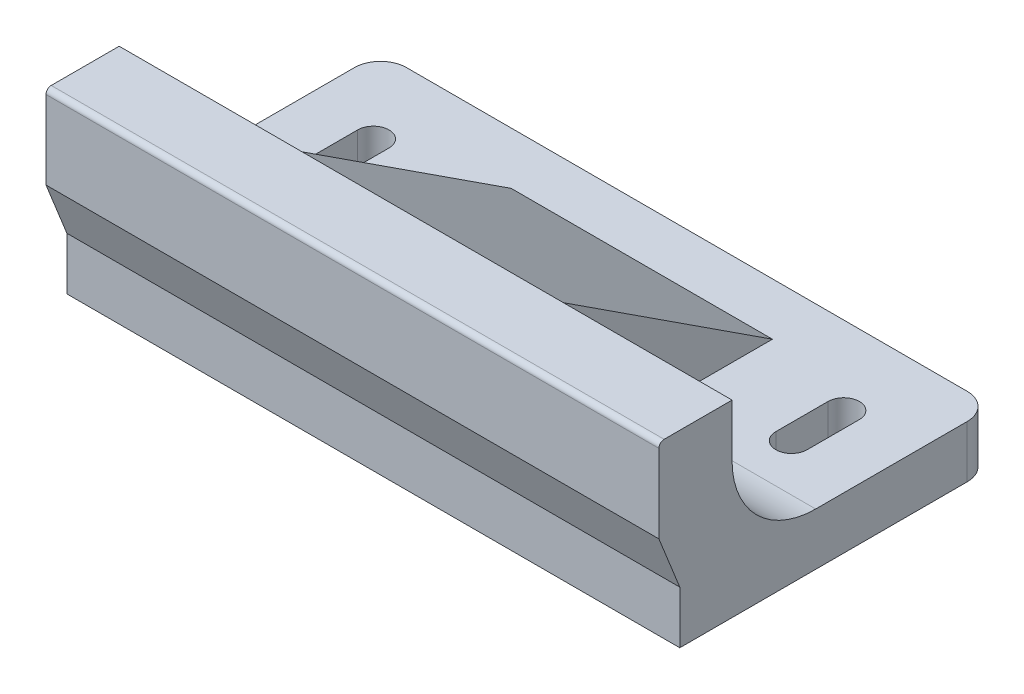
SolidWorks part; units mm, degrees
ref_plane "Front Plane" through (0, 0, 0) normal (0, 0, 1) x (1, 0, 0)
ref_plane "Top Plane" through (0, 0, 0) normal (0, 1, 0) x (1, 0, 0)
ref_plane "Right Plane" through (0, 0, 0) normal (1, 0, 0) x (0, 0, -1)
sketch "Sketch1" plane through (0, 0, 0) normal (0, 1, 0) x (1, 0, 0)
  line L1 (0, 0) -> (117.2727, 0)
  line L2 (0, 0) -> (0, 60)
  line L3 (0, 60) -> (117.2727, 60)
  line L4 (117.2727, 0) -> (117.2727, 60)
  line L5 (0, 0) -> (117.2727, 60) construction
  line L6 (0, 60) -> (117.2727, 0) construction
  point P4 (58.6364, 30)
  dimension "D1" = 60
extrude "Boss-Extrude1" add sketch "Sketch1" along normal blind 10
sketch "Sketch2" plane through (0, 0, 0) normal (0, 0, 1) x (1, 0, 0)
  line L0 (117.2727, 10) -> (117.2727, 0) construction
  line L1 (0, 10) -> (117.2727, 10)
  line L2 (0, 10) -> (0, 19.05)
  line L3 (0, 19.05) -> (117.2727, 19.05)
  line L4 (117.2727, 10) -> (117.2727, 19.05)
  line L5 (0, 10) -> (117.2727, 19.05) construction
  line L6 (0, 19.05) -> (117.2727, 10) construction
  line L7 (0, 0) -> (117.2727, 0) construction
  point P4 (58.6364, 14.525)
  dimension "D1" = 19.05
extrude "Boss-Extrude2" add sketch "Sketch2" against normal blind 10
sketch "Sketch3" plane through (0, 10, 0) normal (0, 1, 0) x (1, 0, 0)
  line L0 (13.6364, 40) -> (103.6364, 40) construction
  line L1 (0, 10) -> (117.2727, 10) construction
  line L2 (58.6364, 10) -> (58.6364, 40) construction
  line L3 (58.6364, 40) -> (58.6364, 60) construction
  line L4 (117.2727, 60) -> (0, 60) construction
  line L5 (13.6364, 45) -> (13.6364, 35) construction
  line L6 (16.6364, 45) -> (16.6364, 35)
  line L7 (10.6364, 45) -> (10.6364, 35)
  line L8 (103.6364, 45) -> (103.6364, 35) construction
  line L9 (100.6364, 45) -> (100.6364, 35)
  line L10 (106.6364, 45) -> (106.6364, 35)
  circle A0 centre (103.6364, 40) radius 3 construction
  circle A1 centre (13.6364, 40) radius 3 construction
  arc A2 (16.6364, 45) -> (10.6364, 45) centre (13.6364, 45) ccw
  arc A3 (10.6364, 35) -> (16.6364, 35) centre (13.6364, 35) ccw
  arc A4 (100.6364, 45) -> (106.6364, 45) centre (103.6364, 45) cw
  arc A5 (106.6364, 35) -> (100.6364, 35) centre (103.6364, 35) cw
  point P4 (58.6364, 10)
  point P5 (58.6364, 40)
  point P14 (13.6364, 40)
  point P20 (0, 0)
  point P21 (13.6364, 35.2792)
  point P24 (103.6364, 40)
  dimension "D1" = 6
  dimension "D2" = 90
  dimension "D3" = 20
  dimension "D4" = 0
  dimension "D5" = 10
extrude "Cut-Extrude1" cut sketch "Sketch3" against normal through all
sketch "Sketch4" plane through (0, 0, 0) normal (0, 0, 1) x (1, 0, 0)
  line L0 (117.2727, 19.05) -> (117.2727, 0) construction
  line L1 (0, 19.05) -> (117.2727, 19.05)
  line L2 (0, 19.05) -> (0, 36.05)
  line L3 (0, 36.05) -> (117.2727, 36.05)
  line L4 (117.2727, 19.05) -> (117.2727, 36.05)
  line L5 (0, 19.05) -> (117.2727, 36.05) construction
  line L6 (0, 36.05) -> (117.2727, 19.05) construction
  point P4 (58.6364, 27.55)
  dimension "D1" = 17
extrude "Boss-Extrude3" add sketch "Sketch4" against normal up to surface (10 mm away) up to face at (58.6364, 14.525, -10)
fillet "Fillet1" radius 16 1 edges at (58.6364, 10, -10)
sketch "Sketch6" plane through (0, 0, 0) normal (-1, 0, 0) x (0, 0, 1)
  line L0 (-50, 10) -> (-10, 36.05)
  line L1 (-60, 10) -> (-26, 10) construction
  line L2 (-10, 36.05) -> (-10, 26) construction
  line L3 (-50, 10) -> (-26, 10)
  line L4 (-10, 36.05) -> (-10, 26)
  line L5 (-50, 10) -> (-50, 36.05) construction
  line L6 (-50, 36.05) -> (-10, 36.05) construction
  line L7 (-10, 36.05) -> (0, 36.05) construction
  arc A0 (-26, 10) -> (-10, 26) centre (-26, 26) ccw construction
  arc A1 (-26, 10) -> (-10, 26) centre (-26, 26) ccw
  point P7 (0, 0)
  line M10 (-10, 36.05) -> (-10, 26)
  arc M11 (-10, 26) -> (-26, 10) centre (-26, 26) cw
  line M12 (-26, 10) -> (-60, 10)
  dimension "D1" = 0
  dimension "D2" = 40
extrude "Boss-Extrude4" add sketch "Sketch6" against normal blind 50 from offset 35 contours L0 M12 M11 M10 region at (0, 19.2856, -24.4837) offset against normal yes
sketch "Sketch7" plane through (0, 0, 0) normal (-1, 0, 0) x (0, 0, 1)
  line L1 (0, 36.05) -> (4, 36.05)
  line L2 (0, 36.05) -> (0, 20.05)
  line L3 (0, 20.05) -> (4, 20.05)
  line L4 (4, 36.05) -> (4, 20.05)
  line L5 (0, 36.05) -> (4, 20.05) construction
  line L6 (0, 20.05) -> (4, 36.05) construction
  point P4 (2, 28.05)
  dimension "D1" = 16
  dimension "D2" = 4
extrude "Boss-Extrude5" add sketch "Sketch7" against normal up to surface (117.2727 mm away) up to face at (117.2727, 16.398, -23.2409)
chamfer "Chamfer1" distance 4 distance2 10 1 edges at (58.6364, 20.05, 0) first distance on face at (58.6364, 20.05, 2)
fillet "Fillet3" radius 1 1 edges at (58.6364, 36.05, 4)
fillet "Fillet4" radius 5 2 edges at (0, 5, -60) (117.2727, 5, -60)
